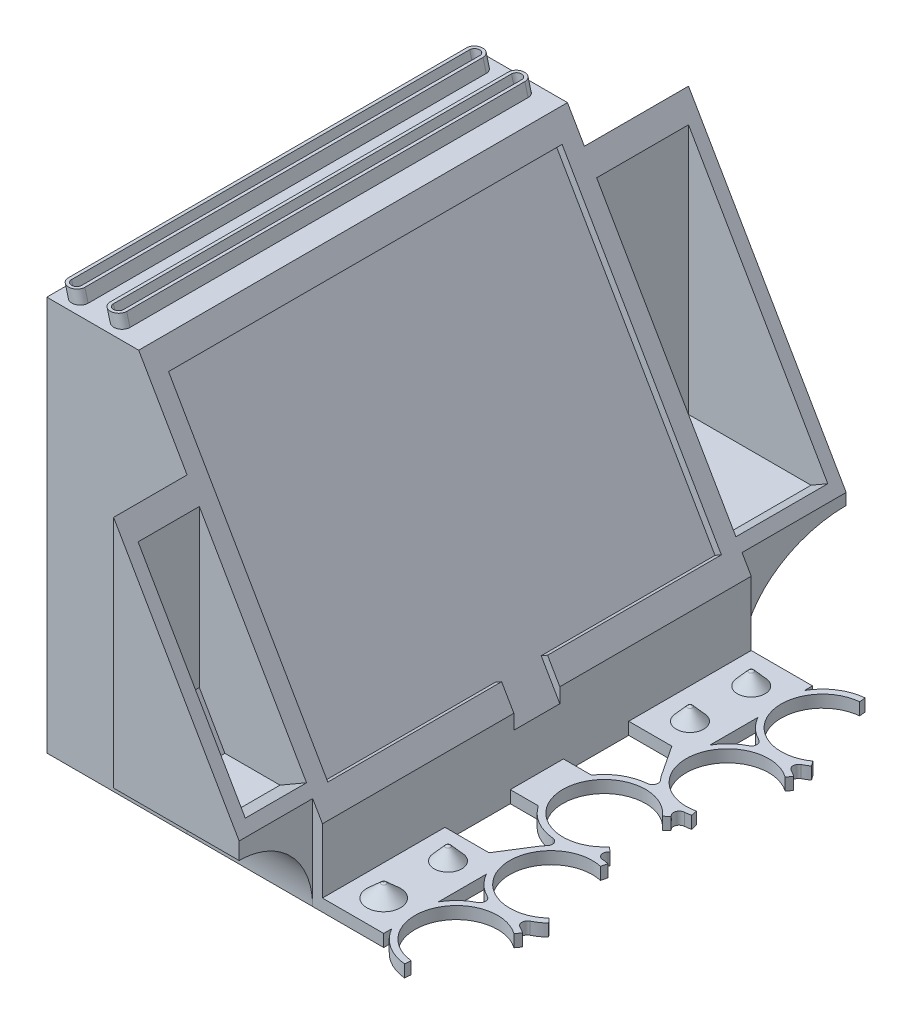
SolidWorks part; units mm, degrees
ref_plane "Front Plane" through (0, 0, 0) normal (0, 0, 1) x (1, 0, 0)
ref_plane "Top Plane" through (0, 0, 0) normal (0, 1, 0) x (1, 0, 0)
ref_plane "Right Plane" through (0, 0, 0) normal (1, 0, 0) x (0, 0, -1)
sketch "Sketch1" plane through (0, 0, 0) normal (0, 0, 1) x (1, 0, 0)
  line L0 (0, 0) -> (90, 0)
  line L1 (90, 0) -> (90, 25)
  line L2 (90, 25) -> (30, 128.923)
  line L4 (0, 128.923) -> (0, 0)
  line L5 (30, 128.923) -> (0, 128.923)
  dimension "D1" = 90
  dimension "D2" = 120
  dimension "D3" = 60
  dimension "D4" = 25
extrude "Boss-Extrude1" add sketch "Sketch1" along normal blind 140
sketch "Sketch2" plane through (78.3253, 45.2211, 0) normal (0.866, 0.5, 0) x (0, 0, -1)
  line L0 (-140, -23.3494) -> (-140, 96.6506) construction
  line L1 (-5.75, 88.6506) -> (-134.25, 88.6506)
  line L2 (-5.75, 88.6506) -> (-5.75, -15.3494)
  line L3 (-5.75, -15.3494) -> (-62.5, -15.3494)
  line L4 (-134.25, 88.6506) -> (-134.25, -15.3494)
  line L5 (-5.75, 88.6506) -> (-134.25, -15.3494) construction
  line L6 (-5.75, -15.3494) -> (-134.25, 88.6506) construction
  line L8 (-140, -23.3494) -> (0, -23.3494) construction
  line L9 (-77.5, -15.3494) -> (-134.25, -15.3494)
  line L11 (-77.5, -15.3494) -> (-77.5, -30.3494)
  line L12 (-77.5, -30.3494) -> (-62.5, -30.3494)
  line L13 (-62.5, -15.3494) -> (-62.5, -30.3494)
  point P0 (-70, 36.6506)
  point P9 (-70, -15.3494)
  dimension "D1" = 128.5
  dimension "D2" = 104
  dimension "D3" = 70
  dimension "D4" = 60
  dimension "D5" = 15
extrude "Cut-Extrude1" cut sketch "Sketch2" against normal blind 2.4
sketch "Sketch3" plane through (0, 0, 0) normal (0, 0, -1) x (-1, 0, 0)
  line L0 (-85, 33.6603) -> (-79.5263, 30.5)
  line L1 (-90, 25) -> (-30, 128.923) construction
  line L2 (-79.5263, 30.5) -> (-39.5263, 30.5)
  line L3 (-39.5263, 30.5) -> (-39.5263, 112.423)
  line L4 (-87, 30.1962) -> (-80.5981, 26.5)
  line L5 (-80.5981, 26.5) -> (-35.5263, 26.5)
  line L6 (-35.5263, 26.5) -> (-35.5263, 112.423)
  line L7 (-35.5263, 112.423) -> (-35.5263, 119.3513)
  line L8 (-35.5263, 119.3513) -> (-39.5263, 112.423)
  line L9 (-87, 30.1962) -> (-85, 33.6603)
  line L10 (0, 0) -> (-90, 0) construction
  dimension "D1" = 40
  dimension "D2" = 30.5
  dimension "D3" = 90
  dimension "D4" = 4
extrude "Boss-Extrude2" add sketch "Sketch3" along normal blind 30
sketch "Sketch4" plane through (0, 0, -30) normal (0, 0, -1) x (-1, 0, 0)
  line L0 (-87, 30.1962) -> (-35.5263, 119.3513)
  line L1 (-35.5263, 119.3513) -> (-35.5263, 26.5)
  line L2 (-35.5263, 26.5) -> (-80.5981, 26.5)
  line L3 (-80.5981, 26.5) -> (-87, 30.1962)
extrude "Boss-Extrude3" add sketch "Sketch4" along normal blind 4
sketch "Sketch5" plane through (0, 0, 140) normal (0, 0, 1) x (1, 0, 0)
  line L0 (84.8038, 34) -> (76.1436, 29)
  line L1 (90, 25) -> (30, 128.923) construction
  line L2 (76.1436, 29) -> (58.1436, 29)
  line L3 (58.1436, 29) -> (49.8038, 43.4449)
  line L4 (49.8038, 43.4449) -> (49.8038, 94.6218)
  line L5 (86.8038, 30.5359) -> (77.2154, 25)
  line L6 (77.2154, 25) -> (55.8342, 25)
  line L7 (55.8342, 25) -> (45.8038, 42.3731)
  line L8 (45.8038, 42.3731) -> (45.8038, 94.6218)
  line L9 (45.8038, 94.6218) -> (45.8038, 101.55)
  line L10 (45.8038, 101.55) -> (49.8038, 94.6218)
  line L11 (84.8038, 34) -> (86.8038, 30.5359)
  line L12 (0, 0) -> (90, 0) construction
  dimension "D1" = 29
  dimension "D2" = 35
  dimension "D3" = 18
  dimension "D4" = 10
  dimension "D5" = 4
extrude "Boss-Extrude4" add sketch "Sketch5" along normal blind 20
sketch "Sketch9" plane through (0, 0, 160) normal (0, 0, 1) x (1, 0, 0)
  line L0 (45.8038, 101.55) -> (45.8038, 42.3731)
  line L1 (45.8038, 42.3731) -> (55.8342, 25)
  line L2 (55.8342, 25) -> (77.2154, 25)
  line L3 (55.8342, 25) -> (77.2154, 25) construction
  line L4 (77.2154, 25) -> (86.8038, 30.5359)
  line L5 (86.8038, 30.5359) -> (84.8038, 34)
  line L10 (49.8038, 94.6218) -> (45.8038, 101.55)
  line L11 (45.8038, 101.55) -> (84.8038, 34)
  line M1 (86.8038, 30.5359) -> (84.8038, 34)
  line M2 (84.8038, 34) -> (76.1436, 29)
  line M3 (76.1436, 29) -> (58.1436, 29)
  line M4 (58.1436, 29) -> (49.8038, 43.4449)
  line M5 (49.8038, 43.4449) -> (49.8038, 94.6218)
  line M6 (49.8038, 94.6218) -> (45.8038, 101.55)
  line M7 (45.8038, 101.55) -> (45.8038, 42.3731)
  line M8 (45.8038, 42.3731) -> (55.8342, 25)
  line M9 (55.8342, 25) -> (77.2154, 25)
  line M10 (77.2154, 25) -> (86.8038, 30.5359)
extrude "Boss-Extrude7" add sketch "Sketch9" along normal blind 4 contours L11 M5 M4 M3 M2 | M10 M1 M2 M3 M4 M5 M6 M7 M8 M9 region at (47.0518, 97.6517, 160) region at (62.4354, 52.2698, 160)
sketch "Sketch6" plane through (0, 0, 0) normal (0, -1, 0) x (-1, 0, 0)
  line L1 (-86.8038, -140) -> (-45.8038, -140)
  line L2 (-86.8038, -140) -> (-86.8038, -164)
  line L3 (-86.8038, -164) -> (-45.8038, -164)
  line L4 (-45.8038, -140) -> (-45.8038, -164)
extrude "Boss-Extrude5" add sketch "Sketch6" against normal up to body separate body
sketch "Sketch7" plane through (0, 0, 0) normal (0, -1, 0) x (1, 0, 0)
  line L1 (87, 0) -> (35.5263, 0)
  line L2 (87, 0) -> (87, -34)
  line L3 (87, -34) -> (35.5263, -34)
  line L4 (35.5263, 0) -> (35.5263, -34)
extrude "Boss-Extrude6" add sketch "Sketch7" against normal up to body separate body
sketch "Sketch12" plane through (90, 0, 0) normal (1, 0, 0) x (0, 0, -1)
  line L2 (-160, 29) -> (-140, 29) construction
  line L5 (30, 30.5) -> (0, 30.5) construction
  ellipse E0 centre (-164, 0) end of major axis (-164, 25) minor radius 24
  ellipse E1 centre (34, 0) end of major axis (0, 0) minor radius 26.5
  dimension "D1" = 4
  dimension "D2" = 4
extrude "Cut-Extrude3" cut sketch "Sketch12" against normal blind 80
sketch "Sketch13" plane through (0, 0, 0) normal (0, 1, 0) x (1, 0, 0)
  line L1 (90, -140) -> (110, -140)
  line L2 (90, -140) -> (90, -100)
  line L3 (90, -100) -> (110, -100)
  line L4 (110, -140) -> (110, -100)
  line L5 (90, 0) -> (110, 0)
  line L6 (90, 0) -> (90, -40)
  line L7 (90, -40) -> (110, -40)
  line L8 (110, 0) -> (110, -40)
  dimension "D1" = 40
  dimension "D2" = 40
  dimension "D3" = 20
  dimension "D4" = 20
extrude "Boss-Extrude9" add sketch "Sketch13" along normal blind 4
sketch "Sketch15" plane through (0, 4, 0) normal (0, 1, 0) x (1, 0, 0)
  line L0 (90, -100) -> (90, -140) construction
  line L1 (90, -140) -> (110, -140) construction
  line L2 (110, -100) -> (90, -100) construction
  line L3 (90, -40) -> (110, -40) construction
  line L4 (110, 0) -> (90, 0) construction
  circle A0 centre (100, -130) radius 5.5
  circle A1 centre (100, -109) radius 4.5
  circle A2 centre (100, -30) radius 4.5
  circle A3 centre (100, -10) radius 4.5
  dimension "D1" = 10
  dimension "D2" = 10
  dimension "D3" = 9
  dimension "D4" = 10
  dimension "D5" = 10
  dimension "D6" = 11
  dimension "D7" = 9
  dimension "D8" = 9
  dimension "D9" = 9
extrude "Boss-Extrude11" add sketch "Sketch15" along normal blind 4.5
ref_plane "Plane1" through (0, 0, 130) normal (0, 0, 1) x (1, 0, 0)
ref_plane "Plane2" through (0, 0, 109) normal (0, 0, -1) x (-1, 0, 0)
ref_plane "Plane3" through (0, 0, 10) normal (0, 0, -1) x (-1, 0, 0)
ref_plane "Plane4" through (0, 0, 30) normal (0, 0, 1) x (1, 0, 0)
sketch "Sketch16" plane through (0, 0, 130) normal (0, 0, 1) x (1, 0, 0)
  line L0 (100.5, 8.5) -> (105.5, 4)
  line L5 (100.5, 8.5) -> (105.5, 8.5)
  line L6 (105.5, 8.5) -> (105.5, 4)
  dimension "D1" = 5
ref_axis "Axis1" through (100, 8.5, 130) along (0, -1, 0)
ref_axis "Axis2" through (100, 8.5, 109) along (0, -1, 0)
ref_axis "Axis3" through (100, 8.5, 30) along (0, -1, 0)
ref_axis "Axis4" through (100, 8.5, 10) along (0, -1, 0)
revolve "Cut-Revolve3" cut sketch "Sketch16" angle 360 about axis through (100, 8.5, 130) along (0, -1, 0)
sketch "Sketch18" plane through (0, 0, 109) normal (0, 0, -1) x (-1, 0, 0)
  line L0 (-104.5, 8.5) -> (-104.5, 4)
  line L1 (-90, 4) -> (-110, 4) construction
  line L2 (-104.5, 8.5) -> (-104.5, 4) construction
  line L3 (-104.5, 4) -> (-100.5, 8.5)
  line L4 (-100.5, 8.5) -> (-104.5, 8.5)
revolve "Cut-Revolve4" cut sketch "Sketch18" angle 360 about axis through (100, 8.5, 109) along (0, -1, 0)
sketch "Sketch19" plane through (0, 0, 30) normal (0, 0, 1) x (1, 0, 0)
  line L0 (104.5, 8.5) -> (104.5, 4)
  line L1 (90, 4) -> (110, 4) construction
  line L2 (104.5, 4) -> (104.5, 8.5) construction
  line L3 (104.5, 4) -> (100.5, 8.5)
  line L4 (100.5, 8.5) -> (104.5, 8.5)
revolve "Cut-Revolve7" cut sketch "Sketch19" angle 360 about axis through (100, 8.5, 30) along (0, -1, 0)
sketch "Sketch20" plane through (0, 0, 10) normal (0, 0, -1) x (-1, 0, 0)
  line L0 (-104.5, 8.5) -> (-104.5, 4)
  line L1 (-90, 4) -> (-110, 4) construction
  line L2 (-104.5, 4) -> (-100.5, 8.5)
  line L3 (-100.5, 8.5) -> (-104.5, 8.5)
revolve "Cut-Revolve8" cut sketch "Sketch20" angle 360 about axis through (100, 8.5, 10) along (0, -1, 0)
fillet "Fillet2" radius 1 4 edges at (100, 8.5, 130.5) (100, 8.5, 109.5) (100, 8.5, 30.5) (100, 8.5, 10.5)
ref_plane "Plane6" through (0, 138.923, 0) normal (0, 1, 0) x (1, 0, 0)
sketch "Sketch23" plane through (0, 138.923, 0) normal (0, 1, 0) x (1, 0, 0)
  line L0 (0, -22.8541) -> (0, -93.5504)
  line L1 (0, -140) -> (0, 0) construction
ref_plane "Plane5" through (-34.7308, 129.617, 0) normal (-0.2588, 0.9659, 0) x (0, 0, 1)
sketch "Sketch21" plane through (-34.7308, 129.617, 0) normal (-0.2588, 0.9659, 0) x (0, 0, 1)
  line L0 (135, 52.1677) -> (5, 52.1677) construction
  line L1 (135, 50.5677) -> (5, 50.5677)
  line L2 (135, 53.7677) -> (5, 53.7677)
  line L3 (135, 52.1677) -> (5, 52.1677) construction
  line L4 (135, 49.5677) -> (5, 49.5677)
  line L5 (135, 54.7677) -> (5, 54.7677)
  line L6 (135, 38.9677) -> (5, 38.9677) construction
  line L7 (135, 37.3677) -> (5, 37.3677)
  line L8 (135, 40.5677) -> (5, 40.5677)
  line L9 (135, 38.9677) -> (5, 38.9677) construction
  line L10 (135, 36.3677) -> (5, 36.3677)
  line L11 (135, 41.5677) -> (5, 41.5677)
  line L15 (140, 33.3677) -> (0, 33.3677) construction
  arc A0 (135, 50.5677) -> (135, 53.7677) centre (135, 52.1677) ccw
  arc A1 (5, 53.7677) -> (5, 50.5677) centre (5, 52.1677) ccw
  arc A2 (135, 49.5677) -> (135, 54.7677) centre (135, 52.1677) ccw
  arc A3 (5, 54.7677) -> (5, 49.5677) centre (5, 52.1677) ccw
  arc A4 (135, 37.3677) -> (135, 40.5677) centre (135, 38.9677) ccw
  arc A5 (5, 40.5677) -> (5, 37.3677) centre (5, 38.9677) ccw
  arc A6 (135, 36.3677) -> (135, 41.5677) centre (135, 38.9677) ccw
  arc A7 (5, 41.5677) -> (5, 36.3677) centre (5, 38.9677) ccw
  point P2 (70, 52.1677)
  point P7 (70, 52.1677)
  point P14 (70, 38.9677)
  point P21 (70, 38.9677)
  dimension "D3" = 1.6
  dimension "D4" = 1.6
  dimension "D6" = 3
  dimension "D1" = 1
  dimension "D2" = 1
  dimension "D8" = 8
sketch "Sketch22" plane through (0, 0, 0) normal (0, 0, -1) x (-1, 0, 0)
  line L0 (-35.5263, 0) -> (-35.5263, 119.3513) construction
  line L1 (-35.5263, 125.923) -> (0, 125.923)
  line L2 (-35.5263, 125.923) -> (-35.5263, 108.3438)
  line L3 (-35.5263, 108.3438) -> (0, 108.3438)
  line L4 (0, 125.923) -> (0, 108.3438)
  line L5 (0, 128.923) -> (0, 0) construction
  line L6 (-30, 128.923) -> (0, 128.923) construction
  dimension "D1" = 3
extrude "Boss-Extrude12" add sketch "Sketch22" along normal blind 10
extrude "Cut-Extrude4" cut sketch "Sketch21" against normal up to surface (13.8369 mm away) contours A5 L7 A4 L8 | L2 A1 L1 A0 up to face at (20.5569, 125.923, -4)
extrude "Boss-Extrude13" add sketch "Sketch21<4>" against normal up to surface (14.268 mm away) up to face at (5.7975, 128.923, 70)
sketch "Sketch21<4>" plane through (-34.7308, 129.617, 0) normal (-0.2588, 0.9659, 0) x (0, 0, 1) same geometry as "Sketch21"
sketch "Sketch24" plane through (0, 138.923, 0) normal (0, 1, 0) x (1, 0, 0)
  line L1 (39.8682, 10.3328) -> (-6.0884, 10.3328)
  line L2 (39.8682, 10.3328) -> (39.8682, -144.7831)
  line L3 (39.8682, -144.7831) -> (-6.0884, -144.7831)
  line L4 (-6.0884, 10.3328) -> (-6.0884, -144.7831)
extrude "Cut-Extrude5" cut sketch "Sketch24" against normal mid plane 12
sketch "Sketch25" plane through (0, 0, -10) normal (0, 0, -1) x (-1, 0, 0)
  line L1 (-35.5263, 108.3438) -> (0, 108.3438)
  line L2 (-35.5263, 108.3438) -> (-35.5263, 125.923)
  line L3 (-35.5263, 125.923) -> (0, 125.923)
  line L4 (0, 108.3438) -> (0, 125.923)
extrude "Cut-Extrude6" cut sketch "Sketch25" against normal blind 10
sketch "Sketch26" plane through (0, 0, 0) normal (0, 1, 0) x (1, 0, 0)
  line L0 (90, -77.5) -> (90, -62.5) construction
  line L1 (90, -140) -> (90, -77.5) construction
  line L2 (34, -5.75) -> (34, -134.25) construction
  line L3 (110, -140) -> (110, -100) construction
  line L4 (90, -62.5) -> (90, 0) construction
  line L5 (110, -40) -> (110, 0) construction
  line L6 (90, -100) -> (90, -40) construction
  line L7 (132.6369, -108.6727) -> (134, -110.1362)
  line L8 (134, -110.1362) -> (132.6369, -108.6727)
  line L9 (132.4982, -117.1773) -> (131.3358, -118.8048)
  line L10 (122, -145.2074) -> (122.1928, -143.2168)
  line L11 (123.8689, -79.9592) -> (122.3368, -78.6736)
  line L12 (123.8689, -60.0408) -> (122.3368, -61.3264)
  line L13 (126.8689, -56.3112) -> (126.4263, -54.3608)
  line L14 (131.3358, -30.259) -> (132.5061, -28.6372)
  line L15 (122, 5.2074) -> (122.1928, 3.2168)
  line L16 (132.4982, -22.8227) -> (131.3358, -21.1952)
  line L17 (126.8689, -83.6888) -> (126.4263, -85.6392)
  line L18 (90, -61.3264) -> (99.1616, -61.3264)
  line L20 (90, -78.6736) -> (99.1616, -78.6736)
  line L22 (104.0757, -40) -> (107.9931, -40)
  line L24 (110.5134, -90.257) -> (104.3835, -100)
  line L25 (110, -100) -> (90, -100) construction
  line L26 (104.3835, -100) -> (107.9931, -100)
  line L27 (90, -78.6736) -> (90, -61.3264)
  line L29 (110.5134, -49.743) -> (104.0757, -40)
  line L30 (90, -40) -> (110, -40) construction
  arc A1 (122.3368, -61.3264) -> (122.3368, -78.6736) centre (112, -70) ccw
  arc A2 (126.4263, -85.6392) -> (132.6369, -108.6727) centre (123.4401, -98.7984) ccw
  arc A3 (131.3358, -30.259) -> (126.4263, -54.3608) centre (123.4401, -41.2016) ccw
  arc A4 (131.3358, -118.8048) -> (122.1928, -143.2168) centre (123.4937, -129.7859) ccw
  arc A5 (122.1928, 3.2168) -> (131.3358, -21.1952) centre (123.4938, -10.2141) ccw
  arc A6 (123.8689, -60.0408) -> (123.5598, -59.6836) centre (112, -70) ccw
  arc A7 (126.8689, -83.6888) -> (124.7695, -83.3618) centre (123.4401, -98.7984) ccw
  arc A8 (132.5061, -28.6372) -> (130.3986, -27.3583) centre (123.4401, -41.2016) ccw
  arc A9 (132.4982, -117.1773) -> (130.4042, -115.9186) centre (123.4937, -129.7859) ccw
  arc A10 (122, 5.2074) -> (116.5353, -24.0574) centre (123.4938, -10.2141) ccw
  arc A11 (130.4042, -115.9186) -> (130.3986, -112.6417) centre (131.2214, -114.2787) cw
  arc A12 (116.5297, -112.6657) -> (116.5353, -115.9426) centre (115.7125, -114.3055) cw
  arc A13 (110.6706, -85.4366) -> (111.8804, -88.482) centre (110.5134, -87.262) cw
  arc A14 (124.7695, -83.3618) -> (123.5598, -80.3164) centre (124.9267, -81.5364) cw
  arc A15 (123.5598, -59.6836) -> (124.7695, -56.6382) centre (124.9267, -58.4636) cw
  arc A16 (111.8804, -51.518) -> (110.6706, -54.5634) centre (110.5134, -52.738) cw
  arc A17 (130.3986, -27.3583) -> (130.4042, -24.0814) centre (131.2214, -25.7213) cw
  arc A18 (116.5353, -24.0574) -> (116.5297, -27.3343) centre (115.7125, -25.6945) cw
  circle A19 centre (123.4401, -41.2016) radius 15.4938 construction
  circle A20 centre (123.4401, -41.2016) radius 13.4938 construction
  circle A21 centre (123.4938, -10.2141) radius 15.4938 construction
  circle A22 centre (123.4938, -10.2141) radius 13.4938 construction
  arc A23 (116.5297, -27.3343) -> (107.9931, -40) centre (123.4401, -41.2016) ccw
  arc A24 (130.4042, -24.0814) -> (132.4982, -22.8227) centre (123.4938, -10.2141) ccw
  circle A25 centre (112, -70) radius 15.4938 construction
  circle A26 centre (112, -70) radius 13.4937 construction
  circle A27 centre (123.4401, -98.7984) radius 15.4938 construction
  circle A28 centre (123.4401, -98.7984) radius 13.4938 construction
  circle A29 centre (123.4937, -129.7859) radius 15.4938 construction
  circle A30 centre (123.4937, -129.7859) radius 13.4938 construction
  arc A31 (116.5353, -115.9426) -> (122, -145.2074) centre (123.4937, -129.7859) ccw
  arc A32 (130.3986, -112.6417) -> (134, -110.1362) centre (123.4401, -98.7984) ccw
  arc A33 (111.8804, -88.482) -> (110.1452, -90.8422) centre (123.4401, -98.7984) ccw
  arc A34 (123.5598, -80.3164) -> (123.8689, -79.9592) centre (112, -70) ccw
  arc A35 (124.7695, -56.6382) -> (126.8689, -56.3112) centre (123.4401, -41.2016) ccw
  arc A36 (110.6706, -54.5634) -> (99.1616, -61.3264) centre (112, -70) ccw
  arc A37 (99.1616, -78.6736) -> (110.6706, -85.4366) centre (112, -70) ccw
  arc A38 (110.5134, -49.743) -> (111.8804, -51.518) centre (123.4401, -41.2016) ccw
  arc A39 (107.9931, -100) -> (116.5297, -112.6657) centre (123.4401, -98.7984) ccw
  point P2 (90, -70)
  point P12 (34, -70)
  dimension "D2" = 26.9875
  dimension "D3" = 26.9875
  dimension "D4" = 26.9875
  dimension "D1" = 22
  dimension "D5" = 26.9875
  dimension "D6" = 26.9875
  dimension "D13" = 50
  dimension "D8" = 12
  dimension "D9" = 150
  dimension "D10" = 24
  dimension "D11" = 12
  dimension "D12" = 150
  dimension "D14" = 50
  dimension "D15" = 3
  dimension "D16" = 3
  dimension "D17" = 0
  dimension "D7" = 2
extrude "Boss-Extrude14" add sketch "Sketch26" along normal blind 4 contours A16 A36 A13 A33 A12 A31 L10 A4 L9 A9 A11 A32 L7 A2 L17 A7 A14 A34 L11 A1 L12 A6 A15 A35 L13 A3 L14 A8 A17 A24 L16 A5 L15 A10 A18 A23 region at (132.1716, 0, 110.4726)
